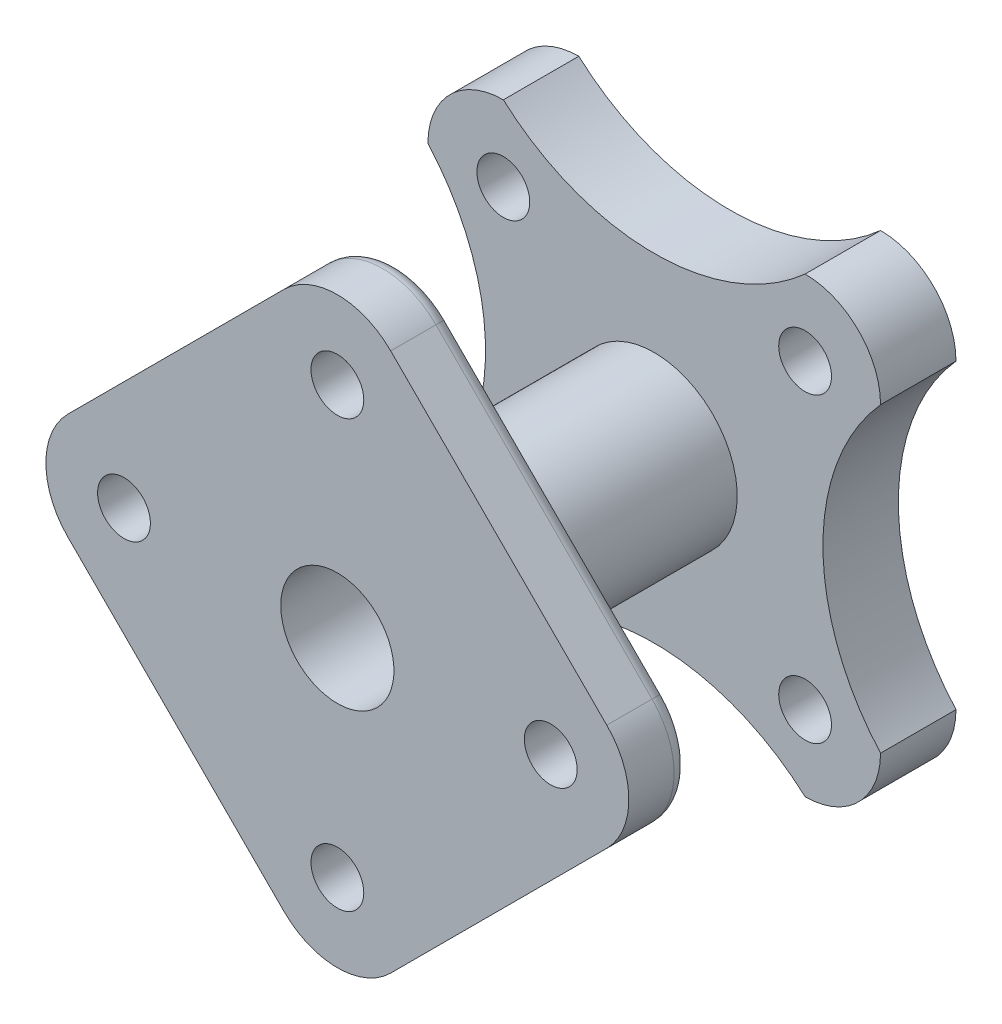
SolidWorks part; units mm, degrees
material "1060 Alloy"
ref_plane "Front Plane" through (0, 0, 0) normal (0, 0, 1) x (1, 0, 0)
ref_plane "Top Plane" through (0, 0, 0) normal (0, 1, 0) x (1, 0, 0)
ref_plane "Right Plane" through (0, 0, 0) normal (1, 0, 0) x (0, 0, -1)
sketch "Sketch1" plane through (0, 0, 0) normal (0, 0, 1) x (1, 0, 0)
  line L0 (10.6961, -43.2693) -> (-25.2249, -7.3483)
  line L1 (-25.2249, 11.0628) -> (10.6961, 46.9838)
  line L2 (29.1072, 46.9838) -> (65.0282, 11.0628)
  line L3 (29.1072, -43.2693) -> (65.0282, -7.3483)
  line L4 (-25.2249, -7.3483) -> (-34.4304, 1.8572)
  line L5 (-34.4304, 1.8572) -> (-25.2249, 11.0628)
  line L6 (10.6961, 46.9838) -> (19.9017, 56.1893)
  line L7 (19.9017, 56.1893) -> (29.1072, 46.9838)
  line L8 (65.0282, 11.0628) -> (74.2338, 1.8572)
  line L9 (74.2338, 1.8572) -> (65.0282, -7.3483)
  line L10 (10.6961, -43.2693) -> (19.9017, -52.4749)
  line L11 (19.9017, -52.4749) -> (29.1072, -43.2693)
  line L12 (-7.2644, 29.0233) -> (47.0677, -25.3088) construction
  line L13 (46.3766, 29.7144) -> (-7.9555, -24.6177) construction
  circle A4 centre (-16.0194, 1.8572) radius 4.445
  circle A5 centre (19.9017, 37.7782) radius 4.445
  circle A6 centre (19.9017, -34.0638) radius 4.445
  circle A7 centre (55.8227, 1.8572) radius 4.445
  point P3 (-7.2644, -25.3088)
  dimension "D2" = 50.8
  dimension "D1" = 50.8
extrude "Boss-Extrude1" add sketch "Sketch1" along normal blind 10.16
fillet "Fillet1" radius 12.7 4 edges at (19.9017, -52.4749, 5.08) (74.2338, 1.8572, 5.08) (-34.4304, 1.8572, 5.08) (19.9017, 56.1893, 5.08)
sketch "Sketch2" plane through (0, 0, 0) normal (0, 0, 1) x (1, 0, 0)
  line L0 (19.9017, 50.9288) -> (19.9017, -47.2144) construction
  arc A0 (28.8819, 47.2091) -> (10.9214, 47.2091) centre (19.9017, 38.2288) ccw construction
  arc A1 (10.9214, -43.4946) -> (28.8819, -43.4946) centre (19.9017, -34.5144) ccw construction
  circle A2 centre (19.9017, 1.8572) radius 13.97
extrude "Boss-Extrude2" add sketch "Sketch2" against normal blind 43.18
sketch "Sketch4" plane through (0, 0, -43.18) normal (0, 0, -1) x (-1, 0, 0)
  circle A0 centre (-45.3017, 27.2572) radius 4.445
  circle A1 centre (5.4983, 27.2572) radius 4.445
  circle A2 centre (5.4983, -23.5428) radius 4.445
  circle A3 centre (-45.3017, -23.5428) radius 4.445
  arc A4 (-45.3017, 39.9572) -> (-58.0017, 27.2572) centre (-45.3017, 27.2572) ccw
  arc A6 (5.4983, 39.9572) -> (18.1983, 27.2572) centre (5.4983, 27.2572) cw
  arc A7 (18.1983, -23.5428) -> (5.4983, -36.2428) centre (5.4983, -23.5428) cw
  arc A8 (-45.3017, -36.2428) -> (-58.0017, -23.5428) centre (-45.3017, -23.5428) cw
  arc A9 (-45.3017, 39.9572) -> (5.4983, 39.9572) centre (-19.9017, 68.3553) ccw
  arc A10 (-58.0017, -23.5428) -> (-58.0017, 27.2572) centre (-86.3997, 1.8572) ccw
  arc A11 (-45.3017, -36.2428) -> (5.4983, -36.2428) centre (-19.9017, -64.6408) cw
  arc A12 (18.1983, -23.5428) -> (18.1983, 27.2572) centre (46.5964, 1.8572) cw
  point P0 (-19.9017, 1.8572)
  dimension "D1" = 50.8
  dimension "D8" = 25.4
  dimension "D2" = 50.8
  dimension "D3" = 50.8
  dimension "D4" = 25.4
  dimension "D5" = 25.4
  dimension "D6" = 50.8
  dimension "D7" = 25.4
extrude "Boss-Extrude3" add sketch "Sketch4" along normal blind 12.7
sketch "Sketch5" plane through (0, 0, -55.88) normal (0, 0, -1) x (-1, 0, 0)
  line L0 (-19.9017, 50.9288) -> (-19.9017, -49.242) construction
  arc A0 (-10.9214, 47.2091) -> (-28.8819, 47.2091) centre (-19.9017, 38.2288) ccw construction
  circle A2 centre (-19.9017, 0.8434) radius 9.525
extrude "Cut-Extrude2" cut sketch "Sketch5" against normal through all
sketch "Sketch6" plane through (0, 0, -55.88) normal (0, 0, -1) x (-1, 0, 0)
  circle A0 centre (-19.9017, 0.8434) radius 19.05
extrude "Cut-Extrude3" cut sketch "Sketch6" against normal blind 2.54
chamfer "Chamfer1" distance 2.54 angle 45 1 edges at (0.8517, 0.8434, -55.88)
fillet "Fillet2" radius 2.54 8 edges at (19.9017, 50.9288, 0) (47.0677, 29.0233, 0) (68.9733, 1.8572, 0) (47.0677, -25.3088, 0) (19.9017, -47.2144, 0) (-7.2644, -25.3088, 0) (-29.1699, 1.8572, 0) (-7.2644, 29.0233, 0)
